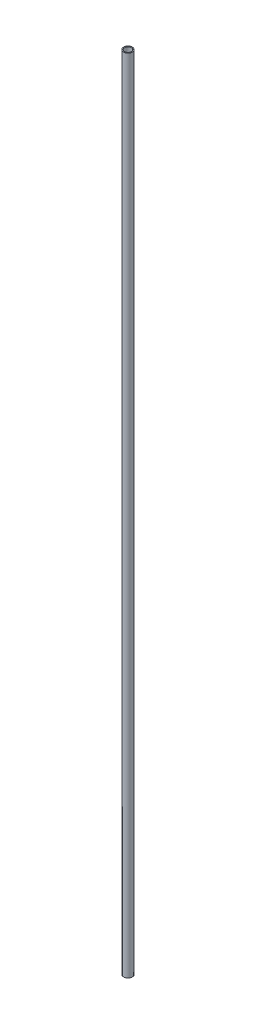
SolidWorks part; units mm, degrees
material "PVC Rigid"
ref_plane "Front Plane" through (0, 0, 0) normal (0, 0, 1) x (1, 0, 0)
ref_plane "Top Plane" through (0, 0, 0) normal (0, 1, 0) x (1, 0, 0)
ref_plane "Right Plane" through (0, 0, 0) normal (1, 0, 0) x (0, 0, -1)
sketch "Sketch1" plane through (0, 0, 0) normal (0, 1, 0) x (1, 0, 0)
  circle A0 centre (0, 0) radius 13.0683
  circle A1 centre (0, 0) radius 16.7005
  dimension "D1" = 33.401
  dimension "D2" = 26.1366
extrude "Boss-Extrude1" add sketch "Sketch1" along normal blind 3048
